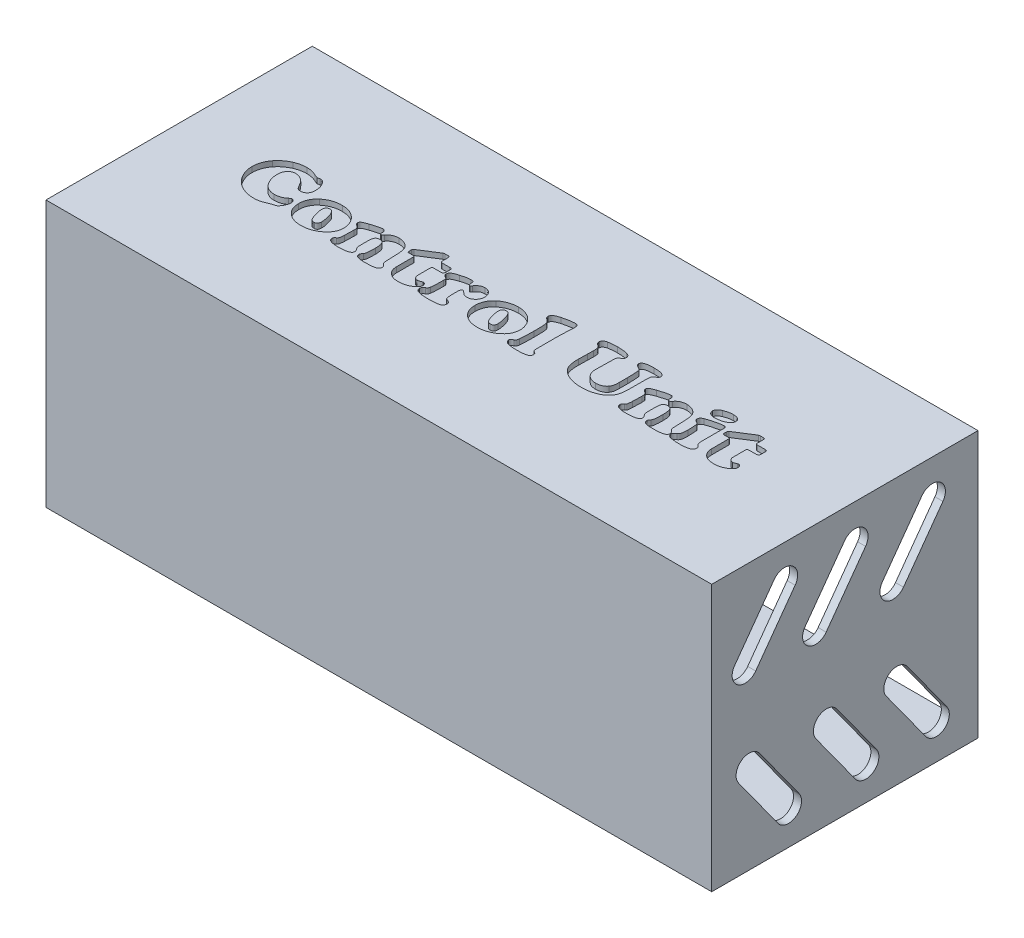
SolidWorks part; units mm, degrees
material "PPS"
ref_plane "Front Plane" through (0, 0, 0) normal (0, 0, 1) x (1, 0, 0)
ref_plane "Top Plane" through (0, 0, 0) normal (0, 1, 0) x (1, 0, 0)
ref_plane "Right Plane" through (0, 0, 0) normal (1, 0, 0) x (0, 0, -1)
sketch "Sketch1" plane through (0, 0, 0) normal (0, 0, 1) x (1, 0, 0)
  line L1 (-125, -50) -> (125, -50)
  line L2 (-125, -50) -> (-125, 50)
  line L3 (-125, 50) -> (125, 50)
  line L4 (125, -50) -> (125, 50)
  line L5 (-125, -50) -> (125, 50) construction
  line L6 (-125, 50) -> (125, -50) construction
  point P0 (0, 0)
  dimension "D1" = 250
  dimension "D2" = 100
extrude "Boss-Extrude1" add sketch "Sketch1" along normal blind 100
sketch "Sketch2" plane through (0, 0, 0) normal (0, 0, -1) x (-1, 0, 0)
  line L0 (-125, 50) -> (125, 50) construction
  line L1 (-122, -47) -> (122, -47)
  line L2 (-122, -47) -> (-122, 47)
  line L3 (-122, 47) -> (122, 47)
  line L4 (122, -47) -> (122, 47)
  line L5 (-122, -47) -> (122, 47) construction
  line L6 (-122, 47) -> (122, -47) construction
  line L7 (-125, -50) -> (-125, 50) construction
  point P0 (0, 0)
  dimension "D1" = 3
  dimension "D2" = 3
extrude "Cut-Extrude1" cut sketch "Sketch2" against normal offset from surface (97 mm away) 3 up to face at (0, 0, 100)
sketch "Sketch3" plane through (0, 50, 0) normal (0, 1, 0) x (1, 0, 0)
  text T0 "Control Unit " font "Cooper Black" height 20
extrude "Cut-Extrude2" cut sketch "Sketch3" against normal blind 2
sketch "Sketch4" plane through (0, -50, 0) normal (0, -1, 0) x (-1, 0, 0)
  text T0 "Control Unit " font "Cooper Black" height 20
extrude "Cut-Extrude3" cut sketch "Sketch4" against normal blind 2
sketch "Sketch5" plane through (-125, 0, 0) normal (-1, 0, 0) x (0, 0, 1)
  line L0 (17.1272, 36.4239) -> (31.9402, 15.9291) construction
  line L1 (21.0849, 39.2844) -> (35.898, 18.7897)
  line L2 (13.1694, 33.5633) -> (27.9825, 13.0686)
  line L3 (46.1718, 36.3088) -> (60.9849, 15.814) construction
  line L4 (50.1296, 39.1693) -> (64.9426, 18.6745)
  line L5 (42.2141, 33.4482) -> (57.0271, 12.9534)
  line L6 (72.6245, 36.9054) -> (87.4376, 16.4107) construction
  line L7 (76.5823, 39.766) -> (91.3953, 19.2712)
  line L8 (68.6668, 34.0449) -> (83.4798, 13.5501)
  arc A0 (21.0849, 39.2844) -> (13.1694, 33.5633) centre (17.1272, 36.4239) ccw
  arc A1 (27.9825, 13.0686) -> (35.898, 18.7897) centre (31.9402, 15.9291) ccw
  arc A2 (50.1296, 39.1693) -> (42.2141, 33.4482) centre (46.1718, 36.3088) ccw
  arc A3 (57.0271, 12.9534) -> (64.9426, 18.6745) centre (60.9849, 15.814) ccw
  arc A4 (76.5823, 39.766) -> (68.6668, 34.0449) centre (72.6245, 36.9054) ccw
  arc A5 (83.4798, 13.5501) -> (91.3953, 19.2712) centre (87.4376, 16.4107) ccw
  point P2 (24.5337, 26.1765)
  point P7 (0, 0)
  point P10 (53.5784, 26.0614)
  point P17 (80.0311, 26.658)
extrude "Cut-Extrude4" cut sketch "Sketch5" against normal through all
sketch "Sketch6" plane through (125, 0, 0) normal (1, 0, 0) x (0, 0, -1)
  line L0 (-85.9669, -16.8225) -> (-71.1538, -37.3173) construction
  line L1 (-82.0091, -13.962) -> (-67.1961, -34.4568)
  line L2 (-89.9246, -19.6831) -> (-75.1116, -40.1779)
  line L3 (-56.9222, -16.9377) -> (-42.1092, -37.4324) construction
  line L4 (-52.9645, -14.0771) -> (-38.1514, -34.5719)
  line L5 (-60.88, -19.7982) -> (-46.0669, -40.293)
  line L6 (-30.4695, -16.341) -> (-15.6565, -36.8358) construction
  line L7 (-26.5118, -13.4804) -> (-11.6987, -33.9752)
  line L8 (-34.4273, -19.2015) -> (-19.6142, -39.6963)
  arc A0 (-82.0091, -13.962) -> (-89.9246, -19.6831) centre (-85.9669, -16.8225) ccw
  arc A1 (-75.1116, -40.1779) -> (-67.1961, -34.4568) centre (-71.1538, -37.3173) ccw
  arc A2 (-52.9645, -14.0771) -> (-60.88, -19.7982) centre (-56.9222, -16.9377) ccw
  arc A3 (-46.0669, -40.293) -> (-38.1514, -34.5719) centre (-42.1092, -37.4324) ccw
  arc A4 (-26.5118, -13.4804) -> (-34.4273, -19.2015) centre (-30.4695, -16.341) ccw
  arc A5 (-19.6142, -39.6963) -> (-11.6987, -33.9752) centre (-15.6565, -36.8358) ccw
  point P2 (-78.5603, -27.0699)
  point P7 (-103.0941, -58.3194)
  point P10 (-49.5157, -27.185)
  point P17 (-23.063, -26.5884)
  point P22 (0, 0)
  point P23 (0, 0)
extrude "Cut-Extrude5" cut sketch "Sketch6" against normal through all
